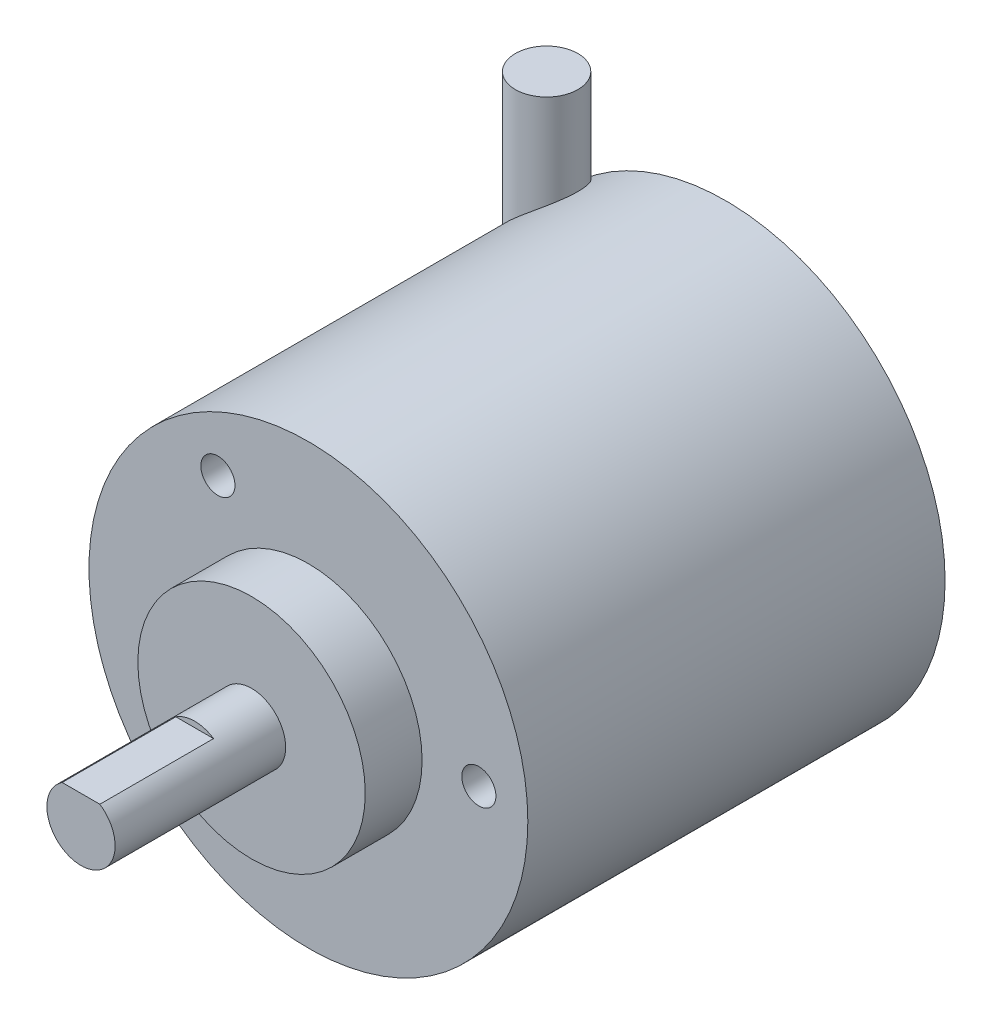
SolidWorks part; units mm, degrees
ref_plane "Front Plane" through (0, 0, 0) normal (0, 0, 1) x (1, 0, 0)
ref_plane "Top Plane" through (0, 0, 0) normal (0, 1, 0) x (1, 0, 0)
ref_plane "Right Plane" through (0, 0, 0) normal (1, 0, 0) x (0, 0, -1)
sketch "Sketch1" plane through (0, 0, 0) normal (0, 0, 1) x (1, 0, 0)
  circle A0 centre (-14.1274, 5.3793) radius 19.3
  dimension "D1" = 38.6
extrude "Boss-Extrude1" add sketch "Sketch1" along normal blind 36.7
sketch "Sketch3" plane through (0, 0, 36.7) normal (0, 0, 1) x (1, 0, 0)
  circle A0 centre (-14.1274, 5.3793) radius 10
  circle A1 centre (-14.1274, 5.3793) radius 19.3 construction
  dimension "D1" = 20
  dimension "D2" = 0
extrude "Boss-Extrude2" add sketch "Sketch3" along normal blind 5
sketch "Sketch4" plane through (0, 0, 41.7) normal (0, 0, 1) x (1, 0, 0)
  circle A0 centre (-14.1274, 5.3793) radius 3
  circle A1 centre (-14.1274, 5.3793) radius 10 construction
  dimension "D1" = 6
  dimension "D2" = 0
extrude "Boss-Extrude3" add sketch "Sketch4" along normal blind 15
sketch "Sketch5" plane through (0, 0, 36.7) normal (0, 0, 1) x (1, 0, 0)
  circle A0 centre (0.863, 5.9165) radius 1.5
  circle A1 centre (-14.1274, 5.3793) radius 3 construction
  circle A2 centre (-21.1574, -7.8714) radius 1.5
  circle A3 centre (-22.0878, 18.0927) radius 1.5
  point P10 (-14.1274, 5.3793)
  dimension "D1" = 3
  dimension "D2" = 15
  dimension "D3" = 3
ref_plane "Plane1" through (0, 24.6793, 0) normal (0, 1, 0) x (1, 0, 0)
sketch "Sketch8" plane through (0, 24.6793, 0) normal (0, 1, 0) x (1, 0, 0)
  circle A0 centre (-26.8321, -3.0426) radius 2.75
  dimension "D1" = 5.5
extrude "Boss-Extrude4" add sketch "Sketch8" against normal blind 15 separate body
sketch "Sketch9" plane through (0, 24.6793, 0) normal (0, 1, 0) x (1, 0, 0)
  circle A0 centre (-26.8321, -3.0426) radius 2.75
extrude "Boss-Extrude5" add sketch "Sketch9" along normal blind 5
extrude "Cut-Extrude1" cut sketch "Sketch5" against normal blind 10
sketch "Sketch10" plane through (0, 0, 56.7) normal (0, 0, 1) x (1, 0, 0)
  line L0 (-15.7857, 7.8793) -> (-12.4691, 7.8793)
  circle A0 centre (-14.1274, 5.3793) radius 3
  point P5 (-12.7147, 8.0258)
  circle M2 centre (-14.1274, 5.3793) radius 3
  dimension "D2" = 6
  dimension "D1" = 2.5
extrude "Cut-Extrude2" cut sketch "Sketch10" against normal blind 10 contours L0 M2 region at (-14.1274, 8.0808, 56.7)
